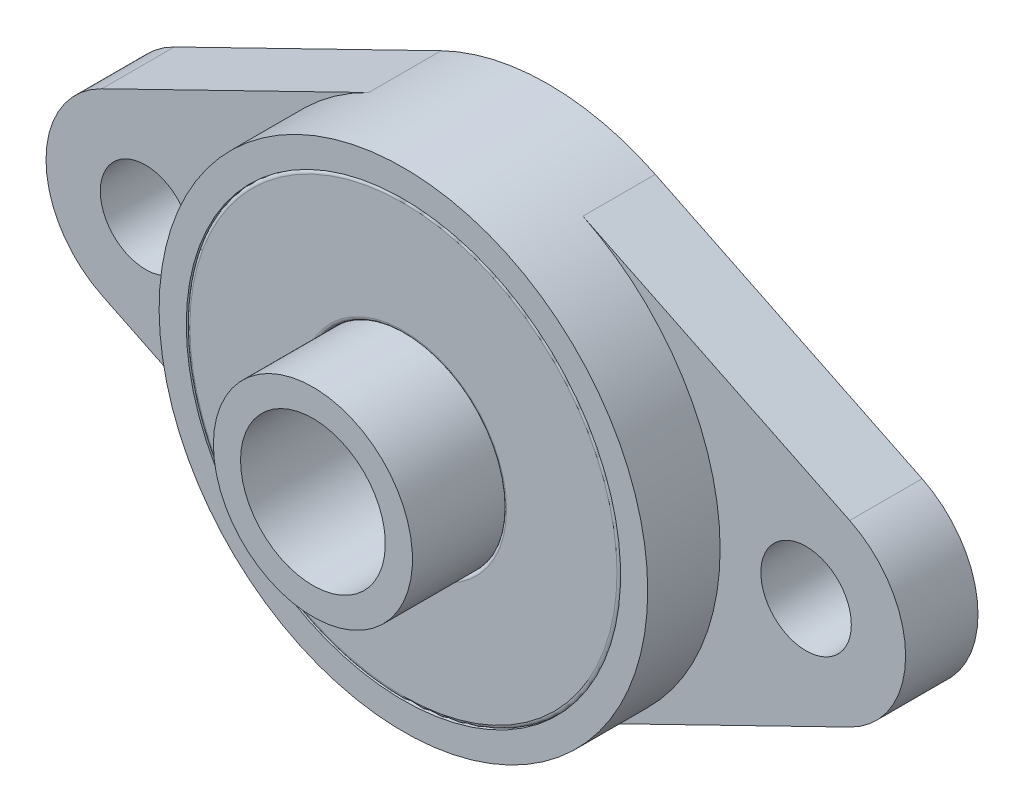
SolidWorks part; units mm, degrees
ref_plane "Front Plane" through (0, 0, 0) normal (0, 0, 1) x (1, 0, 0)
ref_plane "Top Plane" through (0, 0, 0) normal (0, 1, 0) x (1, 0, 0)
ref_plane "Right Plane" through (0, 0, 0) normal (1, 0, 0) x (0, 0, -1)
sketch "Sketch1" plane through (0, 0, 0) normal (0, 0, 1) x (1, 0, 0)
  circle A0 centre (0, 0) radius 13.5
  circle A1 centre (0, 0) radius 12
  circle A2 centre (0, 0) radius 4
  circle A3 centre (0, 0) radius 5.5
  dimension "D1" = 27
  dimension "D3" = 8
  dimension "D2" = 1.5
  dimension "D4" = 1.5
extrude "Boss-Extrude1" add sketch "Sketch1" along normal blind 13 contours A0 A1 | A3 A2 region at (-13.1182, 0, 0) region at (-5.3444, 0, 0)
sketch "Sketch2" plane through (0, 0, 0) normal (0, 0, -1) x (-1, 0, 0)
  line L0 (5.9178, 12.1338) -> (20.661, 4.9434)
  line L1 (20.661, -4.9434) -> (5.9178, -12.1338)
  line L2 (0, 0) -> (18.25, 0) construction
  circle A0 centre (0, 0) radius 13.5 construction
  arc A1 (20.661, 4.9434) -> (20.661, -4.9434) centre (18.25, 0) cw
  arc A2 (5.9178, 12.1338) -> (5.9178, -12.1338) centre (0, 0) cw
  circle A3 centre (18.25, 0) radius 2.5
  dimension "D2" = 5.5
  dimension "D3" = 5
  dimension "D1" = 18.25
extrude "Boss-Extrude3" add sketch "Sketch2" against normal blind 4
mirror "Mirror1" about plane through (0, 0, 0) normal (1, 0, 0) of "Boss-Extrude3"
sketch "Sketch4" plane through (0, 0, 13) normal (0, 0, 1) x (1, 0, 0)
  line L1 (-37, -37) -> (37, -37)
  line L2 (-37, -37) -> (-37, 37)
  line L3 (-37, 37) -> (37, 37)
  line L4 (37, -37) -> (37, 37)
  line L5 (-37, -37) -> (37, 37) construction
  line L6 (-37, 37) -> (37, -37) construction
  circle A0 centre (0, 0) radius 13.5 construction
  circle A1 centre (0, 0) radius 8.75
  point P0 (0, 0)
  dimension "D2" = 17.5
  dimension "D1" = 37
extrude "Cut-Extrude1" cut sketch "Sketch4" against normal offset from surface (5 mm away) 8 up to face at (12, 0, 0)
extrude "Boss-Extrude2" add sketch "Sketch1<3>" along normal blind 8 separate body contours A1 A3 region at (-11.6606, 0, 0)
sketch "Sketch1<3>" plane through (0, 0, 0) normal (0, 0, 1) x (1, 0, 0) same geometry as "Sketch1"
fillet "Fillet6" radius 0.2 4 edges at (12, 0, 0) (5.5, 0, 0) (5.5, 0, 8) (12, 0, 8)
equation "\"d-out\"= 27"
equation "\"d-in\"= 8"
equation "\"t\"= 1.5"
equation "\"b3\"= 13"
equation "\"D1@Sketch1\"=\"d-out\""
equation "\"D3@Sketch1\"=\"d-in\""
equation "\"D4@Sketch1\"=\"t\""
equation "\"D2@Sketch1\"=\"t\""
equation "\"b1\"= 4"
equation "\"D1@Boss-Extrude3\"=\"b1\""
equation "\"D1@Boss-Extrude1\"=\"b3\""
equation "\"b2\"= 8"
equation "\"D1@Sketch4\"=\"d-out\" + 10"
equation "\"D2@Sketch4\"=(\"d-out\" + \"d-in\") / 2"
equation "\"D1@Cut-Extrude1\"=\"b2\""
equation "\"D1@Boss-Extrude2\"=\"b2\""
